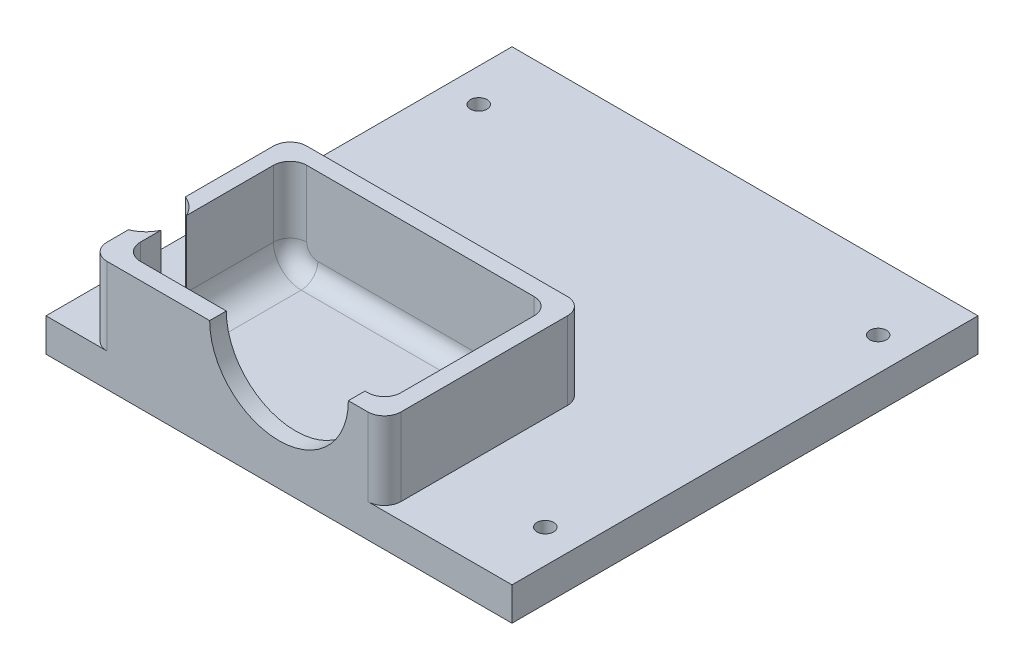
SolidWorks part; units mm, degrees
material "PVB"
ref_plane "Front Plane" through (0, 0, 0) normal (0, 0, 1) x (1, 0, 0)
ref_plane "Top Plane" through (0, 0, 0) normal (0, 1, 0) x (1, 0, 0)
ref_plane "Right Plane" through (0, 0, 0) normal (1, 0, 0) x (0, 0, -1)
sketch "Sketch1" plane through (0, 0, 0) normal (0, 1, 0) x (1, 0, 0)
  line L1 (0, 0) -> (84, 0)
  line L2 (0, 0) -> (0, 84)
  line L3 (0, 84) -> (84, 84)
  line L4 (84, 0) -> (84, 84)
  dimension "D1" = 84
  dimension "D2" = 84
extrude "Boss-Extrude1" add sketch "Sketch1" along normal blind 6
sketch "Sketch2" plane through (0, 6, 0) normal (0, 1, 0) x (1, 0, 0)
  line L0 (84, 84) -> (0, 84) construction
  line L1 (0, 84) -> (0, 0) construction
  line L2 (0, 0) -> (84, 0) construction
  line L3 (84, 0) -> (84, 84) construction
  circle A0 centre (6, 72) radius 1.5
  circle A1 centre (6, 12) radius 1.5
  circle A2 centre (78, 12) radius 1.5
  circle A3 centre (78, 72) radius 1.5
  dimension "D1" = 3
  dimension "D2" = 3
  dimension "D3" = 3
  dimension "D4" = 3
  dimension "D6" = 6
  dimension "D7" = 12
  dimension "D8" = 6
  dimension "D9" = 6
  dimension "D10" = 12
  dimension "D11" = 6
  dimension "D5" = 12
  dimension "D12" = 12
extrude "Cut-Extrude1" cut sketch "Sketch2" against normal through all
ref_plane "Plane1" through (0, 0, -42) normal (0, 0, 1) x (1, 0, 0)
sketch "Sketch4" plane through (0, 6, 0) normal (0, 1, 0) x (1, 0, 0)
  line L0 (3, 21) -> (3, 9)
  line L1 (3, 9) -> (13, 9)
  line L2 (13, 15) -> (8, 21)
  line L3 (3, 21) -> (8, 21)
  line L4 (8, 21) -> (13, 15)
  line L5 (13, 15) -> (13, 9)
  line L6 (0, 84) -> (0, 0) construction
  line L7 (0, 0) -> (84, 0) construction
  circle A0 centre (6, 12) radius 1.5
  circle A1 centre (6, 12) radius 1.5 construction
  dimension "D1" = 3
  dimension "D2" = 9
  dimension "D3" = 12
  dimension "D4" = 10
  dimension "D5" = 6
  dimension "D6" = 5
ref_plane "Plane2" through (42, 0, 0) normal (-1, 0, 0) x (0, 0, 1)
sketch "Sketch5" plane through (0, 6, 0) normal (0, 1, 0) x (1, 0, 0)
  line L0 (8, 36) -> (8, 0)
  line L1 (8, 36) -> (61, 36)
  line L2 (8, 0) -> (61, 0)
  line L3 (61, 36) -> (61, 0)
  line L4 (8, 36) -> (61, 0) construction
  line L5 (8, 0) -> (61, 36) construction
  line L6 (42, 3.3) -> (42, -3.3) construction
  line L12 (0, 0) -> (84, 0) construction
  point P0 (11.3094, 36)
  point P1 (34.5, 18)
  point P9 (42, 18)
  dimension "D1" = 53
  dimension "D2" = 36
  dimension "D3" = 7.5
extrude "Boss-Extrude2" add sketch "Sketch5" along normal blind 22
sketch "Sketch6" plane through (0, 28, 0) normal (0, 1, 0) x (1, 0, 0)
  line L14 (58, 33) -> (11, 33)
  line L15 (11, 33) -> (11, 3)
  line L16 (11, 3) -> (58, 3)
  line L17 (58, 3) -> (58, 33)
  line L18 (58, 33) -> (11, 33)
  line L19 (11, 33) -> (11, 3)
  line L20 (11, 3) -> (58, 3)
  line L21 (58, 3) -> (58, 33)
  dimension "D1" = 3
extrude "Cut-Extrude5" cut sketch "Sketch6" against normal blind 25
fillet "Fillet1" radius 3 10 edges at (58, 15.5, -33) (11, 15.5, -33) (58, 15.5, -3) (11, 15.5, -3) (8, 17, -36) (61, 17, 0) (61, 17, -36) (8, 17, 0) (34.5, 3, -3) (34.5, 3, -33)
fillet "Fillet2" radius 5 6 edges at (11.8787, 3.8787, -3.8787) (11.8787, 3.8787, -32.1213) (57.1213, 3.8787, -32.1213) (57.1213, 3.8787, -3.8787) (58, 3, -18) (11, 3, -18)
sketch "Sketch8" plane through (0, 0, 0) normal (0, 0, 1) x (1, 0, 0)
  line L1 (0, 0) -> (84, 0) construction
  line L3 (61, 28) -> (61, 6) construction
  circle A0 centre (42, 20) radius 12.5
  dimension "D2" = 25
  dimension "D1" = 19
  dimension "D3" = 20
extrude "Cut-Extrude6" cut sketch "Sketch8" against normal blind 10
sketch "Sketch9" plane through (0, 0, 0) normal (0, 0, 1) x (1, 0, 0)
  line L0 (0, 0) -> (84, 0) construction
  line L1 (0, 28) -> (84, 28)
  line L2 (0, 28) -> (0, 20)
  line L3 (0, 20) -> (84, 20)
  line L4 (84, 28) -> (84, 20)
  line L5 (84, 6) -> (84, 0) construction
  line L6 (0, 6) -> (0, 0) construction
  line L7 (11, 28) -> (32.3953, 28) construction
  dimension "D1" = 20
extrude "Cut-Extrude7" cut sketch "Sketch9" against normal through all both and the other way through all
sketch "Sketch11" plane through (0, 0, 0) normal (0, -1, 0) x (1, 0, 0)
  line L0 (3, -9) -> (13, -9)
  line L1 (13, -9) -> (13, -15)
  line L2 (13, -15) -> (8, -21)
  line L3 (8, -21) -> (3, -21)
  line L4 (3, -21) -> (3, -9)
extrude "Cut-Extrude8" cut sketch "Sketch11" against normal blind 3
mirror "Mirror1" about plane through (0, 0, -42) normal (0, 0, 1) of "Cut-Extrude8" second plane through (42, 0, 0) second plane normal (-1, 0, 0)
sketch "Sketch13" plane through (0, 20, 0) normal (0, 1, 0) x (1, 0, 0)
  line L12 (54.5, 0) -> (58, 0)
  line L13 (61, 3) -> (61, 33)
  line L14 (58, 36) -> (11, 36)
  line L15 (8, 33) -> (8, 3)
  line L16 (11, 0) -> (29.5, 0)
  line L17 (29.5, 0) -> (29.5, 3)
  line L18 (29.5, 3) -> (14, 3)
  line L19 (11, 6) -> (11, 30)
  line L20 (14, 33) -> (55, 33)
  line L21 (58, 30) -> (58, 6)
  line L22 (55, 3) -> (54.5, 3)
  line L23 (54.5, 3) -> (54.5, 0)
  line L24 (54.5, 0) -> (58, 0)
  line L25 (61, 3) -> (61, 33)
  line L26 (58, 36) -> (11, 36)
  line L27 (8, 33) -> (8, 3)
  line L28 (11, 0) -> (29.5, 0)
  line L29 (29.5, 0) -> (29.5, 3)
  line L30 (29.5, 3) -> (14, 3)
  line L31 (11, 6) -> (11, 30)
  line L32 (14, 33) -> (55, 33)
  line L33 (58, 30) -> (58, 6)
  line L34 (55, 3) -> (54.5, 3)
  line L35 (54.5, 3) -> (54.5, 0)
  circle A0 centre (6, 12) radius 1.5 construction
  circle A1 centre (6, 12) radius 1.5
  circle A2 centre (6, 12) radius 5.5
  arc A8 (58, 0) -> (61, 3) centre (58, 3) ccw
  arc A9 (61, 33) -> (58, 36) centre (58, 33) ccw
  arc A10 (11, 36) -> (8, 33) centre (11, 33) ccw
  arc A11 (8, 3) -> (11, 0) centre (11, 3) ccw
  arc A12 (11, 6) -> (14, 3) centre (14, 6) ccw
  arc A13 (14, 33) -> (11, 30) centre (14, 30) ccw
  arc A14 (58, 30) -> (55, 33) centre (55, 30) ccw
  arc A15 (55, 3) -> (58, 6) centre (55, 6) ccw
  arc A16 (58, 0) -> (61, 3) centre (58, 3) ccw
  arc A17 (61, 33) -> (58, 36) centre (58, 33) ccw
  arc A18 (11, 36) -> (8, 33) centre (11, 33) ccw
  arc A19 (8, 3) -> (11, 0) centre (11, 3) ccw
  arc A20 (11, 6) -> (14, 3) centre (14, 6) ccw
  arc A21 (14, 33) -> (11, 30) centre (14, 30) ccw
  arc A22 (58, 30) -> (55, 33) centre (55, 30) ccw
  arc A23 (55, 3) -> (58, 6) centre (55, 6) ccw
  dimension "D2" = 11
  dimension "D1" = 0
extrude "Cut-Extrude9" cut sketch "Sketch13" against normal up to surface (14 mm away) contours L27 A2 L31 region at (9.3364, 20, -12) up to face at (6, 6, -70.5)
